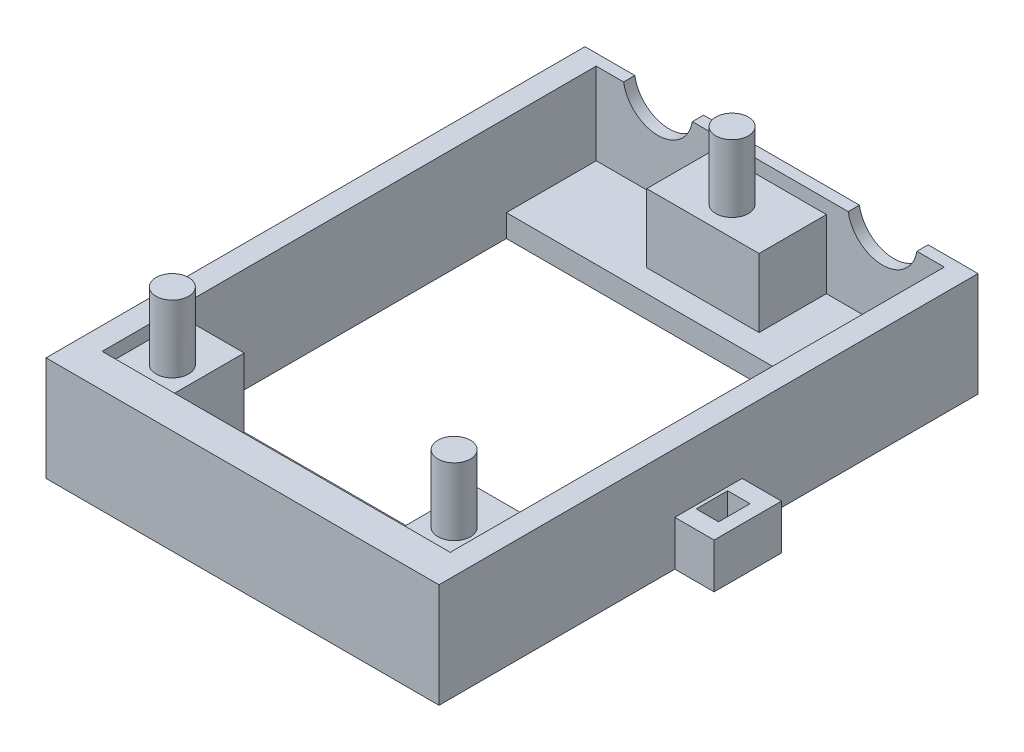
SolidWorks part; units mm, degrees
ref_plane "Front Plane" through (0, 0, 0) normal (0, 0, 1) x (1, 0, 0)
ref_plane "Top Plane" through (0, 0, 0) normal (0, 1, 0) x (1, 0, 0)
ref_plane "Right Plane" through (0, 0, 0) normal (1, 0, 0) x (0, 0, -1)
sketch "Sketch1" plane through (0, 0, 0) normal (0, 1, 0) x (1, 0, 0)
  line L1 (-17.5, 24) -> (17.5, 24)
  line L2 (-17.5, 24) -> (-17.5, -24)
  line L3 (-17.5, -24) -> (17.5, -24)
  line L4 (17.5, 24) -> (17.5, -24)
  line L5 (-44.2539, 0) -> (44.2539, 0) construction
  line L6 (0, -44.7868) -> (0, 44.7868) construction
  dimension "D2" = 35
  dimension "D1" = 48
  dimension "D3" = 24
  dimension "D4" = 17.5
extrude "Boss-Extrude1" add sketch "Sketch1" along normal blind 2
sketch "Sketch2" plane through (0, 2, 0) normal (0, 1, 0) x (1, 0, 0)
  line L1 (-15.5, 23) -> (15.5, 23)
  line L2 (-15.5, 23) -> (-15.5, -21)
  line L3 (-15.5, -21) -> (15.5, -21)
  line L4 (15.5, 23) -> (15.5, -21)
  line L6 (17.5, -24) -> (17.5, 24) construction
  line L7 (-17.5, -24) -> (17.5, -24) construction
  line M5 (-17.5, 24) -> (-17.5, -24)
  line M6 (-17.5, -24) -> (17.5, -24)
  line M7 (17.5, -24) -> (17.5, 24)
  line M8 (17.5, 24) -> (-17.5, 24)
  dimension "D1" = 2
  dimension "D2" = 3
  dimension "D3" = 31
  dimension "D4" = 44
extrude "Boss-Extrude2" add sketch "Sketch2" along normal blind 7.3 contours L1 L4 L3 L2 M8 M5 M6 M7 region at (0, 2, -23.4059)
sketch "Sketch3" plane through (0, 2, 0) normal (0, 1, 0) x (1, 0, 0)
  line L0 (-15.5, 23) -> (15.5, 23) construction
  line L1 (-5, 23) -> (5, 23)
  line L2 (-5, 23) -> (-5, 17)
  line L3 (-5, 17) -> (5, 17)
  line L4 (5, 23) -> (5, 17)
  line L5 (15.5, 23) -> (15.5, -21) construction
  line L7 (-15.5, -21) -> (-10.25, -21)
  line L8 (-15.5, -21) -> (-15.5, -13.6)
  line L9 (-15.5, -13.6) -> (-10.25, -13.6)
  line L10 (-10.25, -21) -> (-10.25, -13.6)
  line L11 (15.5, -21) -> (10.25, -21)
  line L12 (15.5, -21) -> (15.5, -13.6)
  line L13 (15.5, -13.6) -> (10.25, -13.6)
  line L14 (10.25, -21) -> (10.25, -13.6)
  dimension "D1" = 10
  dimension "D2" = 6
  dimension "D3" = 10.5
  dimension "D4" = 5.25
  dimension "D5" = 5.25
  dimension "D6" = 7.4
  dimension "D7" = 7.4
extrude "Boss-Extrude3" add sketch "Sketch3" along normal blind 6.1
sketch "Sketch6" plane through (0, 0, -24) normal (0, 0, -1) x (-1, 0, 0)
  line L1 (-17.5, 9.3) -> (17.5, 9.3) construction
  line L2 (-17.5, 9.3) -> (-17.5, 0) construction
  arc A0 (-6.9406, 9.3) -> (-13.0594, 9.3) centre (-10, 9.8) cw
  arc A1 (13.0594, 9.3) -> (6.9406, 9.3) centre (10, 9.8) cw
  line M3 (17.5, 9.3) -> (-17.5, 9.3)
  dimension "D1" = 7.5
  dimension "D3" = 0.5
  dimension "D4" = 0.5
  dimension "D5" = 3.1
  dimension "D6" = 3.1
  dimension "D2" = 20
sketch "Sketch8" plane through (0, 0, 0) normal (0, 1, 0) x (1, 0, 0)
  line L0 (0, -44.7868) -> (0, 44.7868) construction
  line L1 (-17.5, -24) -> (17.5, -24) construction
  line L2 (17.5, 24) -> (-17.5, 24) construction
  line L4 (-17.5, -24) -> (17.5, -24) construction
  circle A0 centre (-12.55, -17.7) radius 1.45
  circle A1 centre (12.55, -17.7) radius 1.45
  circle A2 centre (0, 19.6) radius 1.45
  dimension "D1" = 2.9
  dimension "D7" = 2.9
  dimension "D8" = 2.9
  dimension "D2" = 6.3
  dimension "D4" = 6.3
  dimension "D3" = 25.1
  dimension "D5" = 12.55
  dimension "D6" = 4.4
sketch "Sketch9" plane through (0, 0, 0) normal (0, 1, 0) x (1, 0, 0)
  line L0 (-35.1135, -20.6) -> (29.9959, -20.6) construction
  line L1 (-15.5, 23) -> (15.5, 23) construction
  line L2 (-35.1135, 21.9) -> (32.5575, 21.9) construction
  point P4 (0, 23)
  dimension "D1" = 43.6
  dimension "D2" = 42.5
extrude "Cut-Extrude5" cut sketch "Sketch6" against normal blind 1 contours A0 M3 | A1 M3 region at (-10, 8.2103, -24) region at (10, 8.2103, -24)
sketch "Sketch10" plane through (0, 2, 0) normal (0, 1, 0) x (1, 0, 0)
  line L0 (-15.5, -13.6) -> (15.5, -13.6)
  line L1 (-15.5, 23) -> (-15.5, -13.6) construction
  line L2 (15.5, 23) -> (15.5, -21) construction
  line L3 (-35.1135, -20.6) -> (29.9959, -20.6) construction
  line L4 (-15.5, 15) -> (15.5, 15)
  line L5 (15.5, 23) -> (15.5, -13.6) construction
  line L6 (-35.1135, 21.9) -> (32.5575, 21.9) construction
  line M5 (15.5, -13.6) -> (15.5, 23)
  line M11 (-15.5, 23) -> (-15.5, -13.6)
  dimension "D1" = 7
  dimension "D2" = 6.9
extrude "Cut-Extrude6" cut sketch "Sketch10" against normal through all contours L4 L0 M11 M5 region at (0, 2, -0.7)
extrude "Boss-Extrude4" add sketch "Sketch8" along normal blind 6 from surface starting at face at (0, 8.1, -20)
sketch "Sketch12" plane through (-17.5, 0, 0) normal (-1, 0, 0) x (0, 0, 1)
  line L0 (0, -44.2539) -> (0, 44.2539) construction
  line L1 (-3, 4) -> (3, 4)
  line L2 (-3, 4) -> (-3, 0)
  line L3 (-3, 0) -> (3, 0)
  line L4 (3, 4) -> (3, 0)
  line L6 (55, 0) -> (-55, 0) construction
  point P6 (0, 0)
  dimension "D1" = 6
  dimension "D2" = 4
  dimension "D3" = 3
extrude "Boss-Extrude5" add sketch "Sketch12" along normal blind 3.5
sketch "Sketch13" plane through (0, 4, 0) normal (0, 1, 0) x (1, 0, 0)
  line L0 (-44.2539, 0) -> (44.2539, 0) construction
  line L1 (-17.8, 1.4) -> (-19.8, 1.4)
  line L2 (-17.8, 1.4) -> (-17.8, -1.4)
  line L3 (-17.8, -1.4) -> (-19.8, -1.4)
  line L4 (-19.8, 1.4) -> (-19.8, -1.4)
  line L6 (-21, -3) -> (-21, 3) construction
  dimension "D1" = 2
  dimension "D2" = 2.8
  dimension "D3" = 1.4
  dimension "D4" = 1.2
extrude "Cut-Extrude7" cut sketch "Sketch13" against normal up to surface (4 mm away) up to face at (-9.625, 0, 0)
mirror "Mirror1" about plane through (0, 0, 0) normal (1, 0, 0) of "Boss-Extrude5", "Cut-Extrude7"
equation "\"fWidth\"=35"
equation "\"D2@Sketch1\"=\"fWidth\""
equation "\"fLength\"= 48"
equation "\"D1@Sketch1\"=\"fLength\""
equation "\"D3@Sketch1\"=\"fLength\"/2"
equation "\"D4@Sketch1\"=\"fWidth\"/2"
equation "\"wThickness\"=2"
equation "\"D1@Sketch2\"=\"wThickness\""
equation "\"D3@Sketch2\"=\"fWidth\"- 2* \"wThickness\""
equation "\"D4@Sketch2\"=\"fLength\"- 2 *\"wThickness\""
equation "\"wHeight\"= 7.3"
equation "\"D1@Boss-Extrude2\"=\"wHeight\""
equation "\"D3@Sketch3\"=(\"fWidth\"- 2 *\"wThickness\" - 10)/2"
equation "\"D1@Boss-Extrude3\"=\"wHeight\""
equation "\"holeDiam\"= 2.9"
equation "\"D8@Sketch8\"=\"holeDiam\""
equation "\"D1@Sketch8\"=\"holeDiam\""
equation "\"D7@Sketch8\"=\"holeDiam\""
